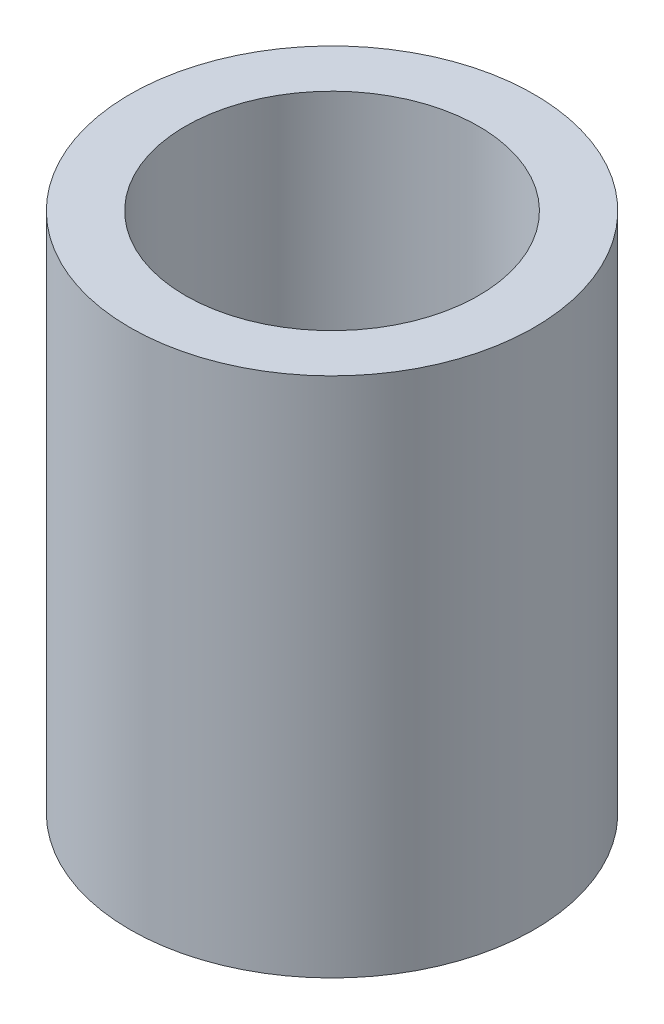
SolidWorks part; units mm, degrees
ref_plane "Front Plane" through (0, 0, 0) normal (0, 0, 1) x (1, 0, 0)
ref_plane "Top Plane" through (0, 0, 0) normal (0, 1, 0) x (1, 0, 0)
ref_plane "Right Plane" through (0, 0, 0) normal (1, 0, 0) x (0, 0, -1)
sketch "Sketch1" plane through (0, 0, 0) normal (0, 1, 0) x (1, 0, 0)
  circle A0 centre (0, 0) radius 3.1
  dimension "D1" = 6.2
extrude "Boss-Extrude1" add sketch "Sketch1" along normal blind 8
sketch "Sketch2" plane through (0, 8, 0) normal (0, 1, 0) x (1, 0, 0)
  circle A0 centre (0, 0) radius 2.25
  dimension "D1" = 4.5
extrude "Cut-Extrude1" cut sketch "Sketch2" against normal through all
